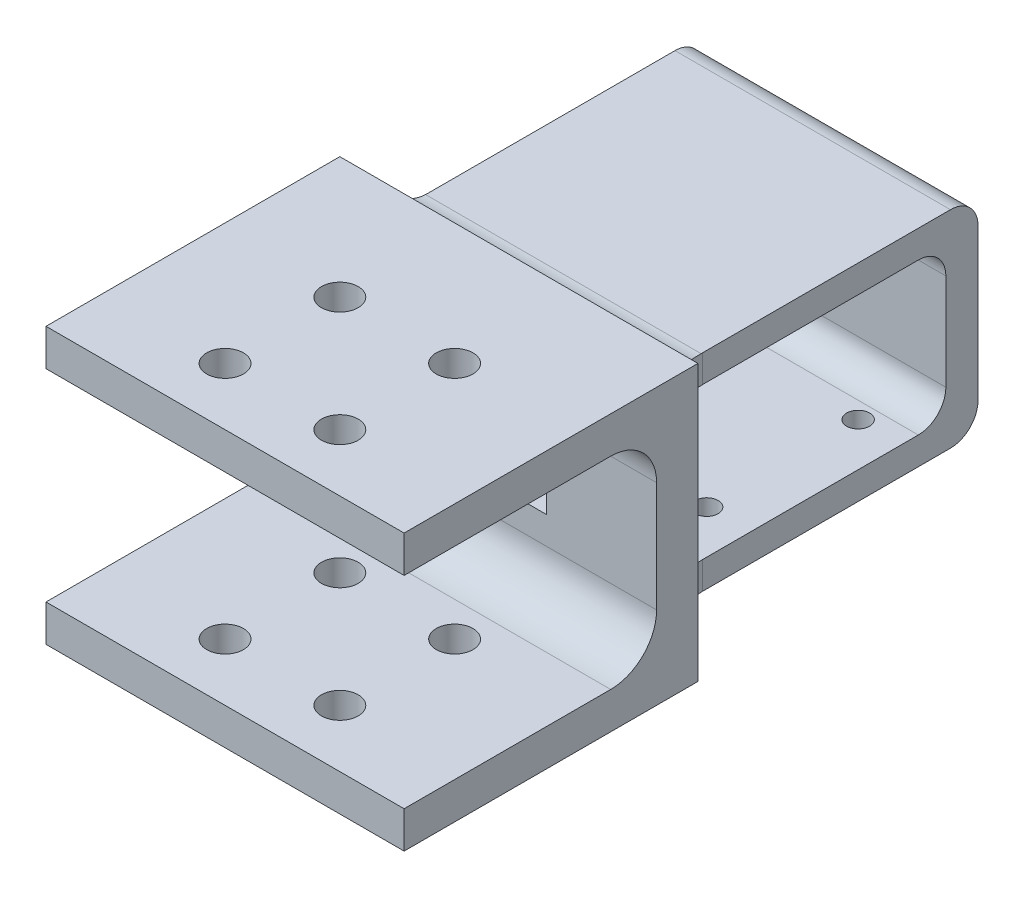
SolidWorks part; units mm, degrees
ref_plane "Front Plane" through (0, 0, 0) normal (0, 0, 1) x (1, 0, 0)
ref_plane "Top Plane" through (0, 0, 0) normal (0, 1, 0) x (1, 0, 0)
ref_plane "Right Plane" through (0, 0, 0) normal (1, 0, 0) x (0, 0, -1)
sketch "Sketch2" plane through (0, 0, 0) normal (0, 0, 1) x (1, 0, 0)
  line L1 (-20, 15) -> (20, 15)
  line L2 (-20, 15) -> (-20, -15)
  line L3 (-20, -15) -> (20, -15)
  line L4 (20, 15) -> (20, -15)
  line L5 (-20, 15) -> (20, -15) construction
  line L6 (-20, -15) -> (20, 15) construction
  point P0 (0, 0)
  dimension "D1" = 30
  dimension "D2" = 40
extrude "Boss-Extrude1" add sketch "Sketch2" along normal blind 40
sketch "Sketch3" plane through (-20, 0, 0) normal (-1, 0, 0) x (0, 0, 1)
  line L0 (0, 0) -> (40, 0) construction
  line L1 (40, 15) -> (40, -15) construction
  line L3 (0, 15) -> (0, -15) construction
  line L4 (40, 15) -> (0, 15) construction
  line L5 (9.5, 11) -> (40, 11)
  line L11 (9.5, -11) -> (40, -11)
  line L12 (4.5, 6) -> (4.5, -6)
  line L13 (40, 11) -> (40, -11)
  arc A2 (9.5, -11) -> (4.5, -6) centre (9.5, -6) cw
  arc A3 (4.5, 6) -> (9.5, 11) centre (9.5, 6) cw
  point P12 (4.5, -11)
  point P14 (0, 11)
  point P20 (4.5, 11)
  dimension "D2" = 5
  dimension "D1" = 4
  dimension "D3" = 4.5
extrude "Cut-Extrude4" cut sketch "Sketch3" against normal through all
fillet "Fillet1" radius 4 2 edges at (0, -15, 0) (0, 15, 0)
ref_plane "Plane1" through (-10, 0, 0) normal (-1, 0, 0) x (0, 0, 1)
sketch "Sketch4" plane through (-10, 0, 0) normal (-1, 0, 0) x (0, 0, 1)
  line L0 (0, 11) -> (-42.1, 11)
  line L1 (-42.1, -11) -> (1.4176, -11)
  line L7 (1.4176, -11) -> (1.4176, 11)
  line L17 (1.4176, 11) -> (0, 11)
  line L24 (0, 14.8516) -> (0, -23.2412) construction
  line L25 (-42.1, 11) -> (-42.1, -11)
  line L26 (-5, -6.1) -> (-37.1, -6.1)
  line L27 (-37.1, 6.1) -> (-37.1, -6.1)
  line L28 (-5, 6.1) -> (-37.1, 6.1)
  line L29 (-5, 6.1) -> (-5, -6.1)
  point P0 (-42.1, 0)
  point P26 (0, -11)
  point P27 (0, 11)
  dimension "D3" = 32.1
  dimension "D1" = 5
  dimension "D2" = 5
  dimension "D4" = 12.2
extrude "Boss-Extrude2" add sketch "Sketch4" along normal blind 8 and the other way blind 10
ref_plane "Plane2" through (-2.5, 0, 0) normal (1, 0, 0) x (0, 0, -1)
sketch "Sketch5" plane through (-2.5, 0, 0) normal (1, 0, 0) x (0, 0, -1)
  line L0 (37.1, -6.1) -> (5, -6.1) construction
  line L1 (5, 6.1) -> (9.2, 6.1)
  line L2 (5, 6.1) -> (5, -6.1)
  line L3 (5, -6.1) -> (9.2, -6.1)
  line L4 (9.2, 6.1) -> (9.2, -6.1)
  line L5 (21.05, 6.1) -> (21.05, -6.1) construction
  line L6 (5, 6.1) -> (37.1, 6.1) construction
  line L7 (32.9, 6.1) -> (32.9, -6.1)
  line L8 (37.1, -6.1) -> (32.9, -6.1)
  line L9 (37.1, 6.1) -> (37.1, -6.1)
  line L10 (37.1, 6.1) -> (32.9, 6.1)
  circle A2 centre (7.25, 0) radius 1.1
  circle A3 centre (34.85, 0) radius 1.1
  dimension "D1" = 4.2
  dimension "D2" = 27.6
extrude "Boss-Extrude3" add sketch "Sketch5" against normal blind 2.5
fillet "Fillet4" radius 0.5 2 edges at (-5, 0, -37.1) (-5, 0, -5)
sketch "Sketch6" plane through (0, 0, 0) normal (1, 0, 0) x (0, 0, -1)
  line L20 (37.8, -6.8) -> (37.8, 6.8)
  line L21 (37.8, 6.8) -> (4.3, 6.8)
  line L22 (4.3, 6.8) -> (4.3, -6.8)
  line L23 (4.3, -6.8) -> (37.8, -6.8)
  line L24 (37.8, -6.8) -> (37.8, 6.8)
  line L25 (37.8, 6.8) -> (4.3, 6.8)
  line L26 (4.3, 6.8) -> (4.3, -6.8)
  line L27 (4.3, -6.8) -> (37.8, -6.8)
  dimension "D1" = 0.7
extrude "Cut-Extrude5" cut sketch "Sketch6" against normal up to surface (2.5 mm away) up to face at (-2.5, 1.1, -7.25)
sketch "Sketch7" plane through (0, 0, -9.2) normal (0, 0, -1) x (-1, 0, 0)
  line L0 (5, 0) -> (15, 0) construction
  line L1 (5, -6.1) -> (5, 6.1) construction
  line L3 (12, 2.25) -> (15, 2.25)
  line L4 (12, 2.25) -> (12, -2.25)
  line L5 (12, -2.25) -> (15, -2.25)
  line L6 (15, 2.25) -> (15, -2.25)
  dimension "D1" = 10
  dimension "D2" = 4.5
  dimension "D3" = 3
extrude "Cut-Extrude6" cut sketch "Sketch7" against normal up to surface and the other way up to surface contours L6 L5 L4 L3 up to face at (0, 0, 4.5) other way up to face at (-9, 0, -42.1)
sketch "Sketch10" plane through (0, 0, 0) normal (1, 0, 0) x (0, 0, -1)
  line L1 (42.1, 11) -> (0, 11)
  line L2 (42.1, 11) -> (42.1, -11)
  line L3 (42.1, -11) -> (0, -11)
  line L4 (0, 11) -> (0, -11)
  line L5 (4.3, 6.8) -> (37.8, 6.8)
  line L6 (4.3, 6.8) -> (4.3, -6.8)
  line L7 (4.3, -6.8) -> (37.8, -6.8)
  line L8 (37.8, 6.8) -> (37.8, -6.8)
extrude "Boss-Extrude5" add sketch "Sketch10" along normal blind 5
fillet "Fillet7" radius 10 2 edges at (-6.5, 11, 0) (-6.5, -11, 0)
sketch "Sketch11" plane through (0, 0, -42.1) normal (0, 0, -1) x (-1, 0, 0)
  line L0 (18, 11) -> (-5, 11) construction
  line L1 (2, 11) -> (-8, 11)
  line L3 (2, -49) -> (-8, -49)
  line L4 (-8, 11) -> (-8, -49)
  line L5 (-5, 11) -> (-5, -11) construction
  line L6 (-5, 11) -> (-5, -11) construction
  line L7 (15, 2.25) -> (15, -2.25) construction
  line L8 (12, -2.25) -> (15, -2.25) construction
  line L9 (12, 2.25) -> (12, -2.25) construction
  line L10 (12, 2.25) -> (15, 2.25) construction
  line L11 (15, 2.25) -> (15, -2.25)
  line L12 (12, -2.25) -> (15, -2.25)
  line L13 (12, 2.25) -> (12, -2.25)
  line L14 (12, 2.25) -> (15, 2.25)
  line L15 (2, 11) -> (18, 11)
  line L16 (18, 11) -> (18, -49)
  line L17 (18, -49) -> (2, -49)
  dimension "D1" = 3
  dimension "D2" = 60
extrude "Boss-Extrude6" add sketch "Sketch11" along normal blind 20
sketch "Sketch14" plane through (0, 11, 0) normal (0, 1, 0) x (1, 0, 0)
  line L0 (1, 62.1) -> (1, 52.1) construction
  line L1 (-18, 62.1) -> (8, 62.1) construction
  line L2 (1, 52.1) -> (8, 52.1) construction
  line L3 (8, 62.1) -> (8, 42.1) construction
  line L4 (2, 55.1) -> (3, 55.1)
  line L6 (-1, 55.1) -> (-1, 49.1)
  line L7 (-1, 49.1) -> (3, 49.1)
  line L8 (3, 55.1) -> (3, 53.1)
  line L9 (-1, 55.1) -> (3, 49.1) construction
  line L10 (-1, 49.1) -> (3, 55.1) construction
  line L19 (3, 51.1) -> (3, 49.1)
  line L27 (0, 65.1) -> (2, 65.1)
  line L29 (0, 65.1) -> (0, 55.1)
  line L30 (2, 65.1) -> (2, 55.1)
  line L31 (3, 53.1) -> (13, 53.1)
  line L32 (13, 53.1) -> (13, 51.1)
  line L33 (13, 51.1) -> (3, 51.1)
  line L34 (-1, 55.1) -> (0, 55.1)
  point P7 (3, 50.1)
  dimension "D1" = 4
  dimension "D2" = 6
  dimension "D3" = 2
  dimension "D4" = 2
  dimension "D5" = 10
  dimension "D6" = 10
  dimension "D7" = 5
extrude "Cut-Extrude7" cut sketch "Sketch14" against normal blind 50
sketch "Sketch17" plane through (0, -39, 0) normal (0, 1, 0) x (1, 0, 0)
  line L1 (-1, 55.1) -> (3, 55.1)
  line L2 (-1, 55.1) -> (-1, 49.1)
  line L3 (-1, 49.1) -> (3, 49.1)
  line L4 (3, 55.1) -> (3, 49.1)
extrude "Cut-Extrude8" cut sketch "Sketch17" against normal blind 1
sketch "Sketch18" plane through (0, 11, 0) normal (0, 1, 0) x (1, 0, 0)
  line L5 (-17, 61.1) -> (7, 61.1)
  line L6 (7, 61.1) -> (7, 43.1)
  line L7 (-17, 43.1) -> (7, 43.1)
  line L8 (-17, 61.1) -> (-17, 43.1)
  line L9 (-18, 5.798) -> (-18, 62.1) construction
  line L10 (-18, 62.1) -> (0, 62.1) construction
  line L11 (8, 51.1) -> (8, 42.1) construction
  line L12 (5, 42.1) -> (8, 42.1) construction
  dimension "D1" = 1
  dimension "D2" = 1
  dimension "D3" = 1
  dimension "D4" = 1
extrude "Cut-Extrude9" cut sketch "Sketch18" against normal blind 1
sketch "Sketch20" plane through (0, 15, 0) normal (0, 1, 0) x (1, 0, 0)
  line L0 (-17.0807, -4) -> (-17.0807, -40) construction
  line L1 (-23.2772, -29) -> (21.5631, -29)
  line L2 (-23.2772, -29) -> (-23.2772, -45.2236)
  line L3 (-23.2772, -45.2236) -> (21.5631, -45.2236)
  line L4 (21.5631, -29) -> (21.5631, -45.2236)
  line L5 (20, -4) -> (-20, -4) construction
  line L6 (20, -40) -> (-20, -40) construction
  dimension "D1" = 36
  dimension "D2" = 25
extrude "Cut-Extrude10" cut sketch "Sketch20" against normal through all
sketch "Sketch23" plane through (-20, 0, 0) normal (-1, 0, 0) x (0, 0, 1)
  line L0 (4.5, 0) -> (34.0631, 0) construction
  line L1 (29, 15) -> (32, 15)
  line L2 (29, 15) -> (29, 11)
  line L3 (29, 11) -> (32, 11)
  line L4 (32, 15) -> (32, 11)
  line L5 (4.5, 6) -> (4.5, -6) construction
  line L6 (29, 11) -> (9.5, 11) construction
  line L7 (32, -15) -> (32, -11)
  line L8 (29, -11) -> (32, -11)
  line L9 (29, -15) -> (29, -11)
  line L10 (29, -15) -> (32, -15)
  dimension "D1" = 3
extrude "Boss-Extrude7" add sketch "Sketch23" against normal up to surface (40 mm away) up to face at (20, 0, 12.356)
sketch "Sketch24" plane through (20, 0, 0) normal (1, 0, 0) x (0, 0, -1)
  line L1 (0, 22.9048) -> (-36.376, 22.9048)
  line L2 (0, 22.9048) -> (0, -20.1823)
  line L3 (0, -20.1823) -> (-36.376, -20.1823)
  line L4 (-36.376, 22.9048) -> (-36.376, -20.1823)
extrude "Cut-Extrude13" cut sketch "Sketch24" against normal up to surface (15 mm away) up to face at (5, 0, -11.6762)
sketch "Sketch25" plane through (-20, 0, 0) normal (-1, 0, 0) x (0, 0, 1)
  line L1 (0, 22.5734) -> (34.945, 22.5734)
  line L2 (0, 22.5734) -> (0, -21.6266)
  line L3 (0, -21.6266) -> (34.945, -21.6266)
  line L4 (34.945, 22.5734) -> (34.945, -21.6266)
extrude "Cut-Extrude14" cut sketch "Sketch25" against normal up to surface (2 mm away) up to face at (-18, 0, -21.05)
ref_plane "Plane3" through (-6.5, 0, 0) normal (-1, 0, 0) x (0, 0, 1)
sketch "Sketch26" plane through (-6.5, 0, 0) normal (-1, 0, 0) x (0, 0, 1)
  line L0 (1.2006, 13.8571) -> (1.2006, -13.8571)
  line L50 (4, -15) -> (32, -15)
  line L51 (32, -15) -> (32, -11)
  line L52 (32, -11) -> (9.5, -11)
  line L53 (4.5, -6) -> (4.5, 6)
  line L54 (9.5, 11) -> (32, 11)
  line L55 (32, 11) -> (32, 15)
  line L56 (32, 15) -> (4, 15)
  line L57 (4, -15) -> (32, -15)
  line L58 (32, -15) -> (32, -11)
  line L59 (32, -11) -> (9.5, -11)
  line L60 (4.5, -6) -> (4.5, 6)
  line L61 (9.5, 11) -> (32, 11)
  line L62 (32, 11) -> (32, 15)
  line L63 (32, 15) -> (4, 15)
  arc A0 (1.2006, -13.8571) -> (-5.798, -11) centre (-5.798, -21) ccw construction
  arc A29 (1.2006, -13.8571) -> (4, -15) centre (4, -11) ccw
  arc A30 (4.5, -6) -> (9.5, -11) centre (9.5, -6) ccw
  arc A31 (9.5, 11) -> (4.5, 6) centre (9.5, 6) ccw
  arc A32 (4, 15) -> (1.2006, 13.8571) centre (4, 11) ccw
  arc A33 (1.2006, -13.8571) -> (4, -15) centre (4, -11) ccw
  arc A34 (4.5, -6) -> (9.5, -11) centre (9.5, -6) ccw
  arc A35 (9.5, 11) -> (4.5, 6) centre (9.5, 6) ccw
  arc A36 (4, 15) -> (1.2006, 13.8571) centre (4, 11) ccw
  dimension "D1" = 0
extrude "Boss-Extrude8" add sketch "Sketch26" along normal blind 20 and the other way blind 20
sketch "Sketch27" plane through (0, 0, -62.1) normal (0, 0, -1) x (-1, 0, 0)
  line L0 (12, -2.25) -> (15, -2.25) construction
  line L1 (15, -2.25) -> (15, 2.25) construction
  line L2 (15, 2.25) -> (12, 2.25) construction
  line L3 (12, -2.25) -> (12, 2.25) construction
  line L4 (12, -2.25) -> (15, -2.25)
  line L5 (15, -2.25) -> (15, 2.25)
  line L6 (15, 2.25) -> (12, 2.25)
  line L7 (12, -2.25) -> (12, 2.25)
extrude "Cut-Extrude15" cut sketch "Sketch27" against normal through all
sketch "Sketch30" plane through (0, 10, 0) normal (0, 1, 0) x (1, 0, 0)
  line L0 (-5, 43.1) -> (-5, 61.1) construction
  line L1 (-17, 43.1) -> (7, 43.1) construction
  line L2 (0, 61.1) -> (-17, 61.1) construction
  line L3 (-17, 52.1) -> (8, 52.1) construction
  line L4 (-17, 61.1) -> (-17, 43.1) construction
  line L5 (8, 51.1) -> (8, 53.1) construction
  line L6 (7, 61.1) -> (2, 61.1) construction
  line L7 (7, 53.1) -> (7, 61.1) construction
  circle A0 centre (5, 58.1) radius 1.2
  circle A1 centre (5, 46.1) radius 1.2
  circle A2 centre (-15, 58.1) radius 1.2
  circle A3 centre (-15, 46.1) radius 1.2
  dimension "D1" = 3
  dimension "D2" = 2
extrude "Cut-Extrude16" cut sketch "Sketch30" against normal blind 5
sketch "Sketch31" plane through (8, 0, 0) normal (1, 0, 0) x (0, 0, -1)
  line L0 (62.1, 11) -> (62.1, -49) construction
  line L1 (42.1, -49) -> (62.1, -49)
  line L2 (42.1, -49) -> (42.1, -44)
  line L3 (42.1, -44) -> (62.1, -44)
  line L4 (62.1, -49) -> (62.1, -44)
  dimension "D1" = 5
extrude "Cut-Extrude17" cut sketch "Sketch31" against normal through all
sketch "Sketch32" plane through (0, -11, 0) normal (0, 1, 0) x (1, 0, 0)
  line L0 (-6.5, -9.5) -> (-6.5, -32) construction
  line L5 (13.5, -9.5) -> (-26.5, -9.5) construction
  line L6 (13.5, -32) -> (-26.5, -32) construction
  line L7 (-26.5, -20.75) -> (-6.5, -20.75) construction
  line L8 (-26.5, -32) -> (-26.5, -9.5) construction
  line L9 (-16.5, -20.75) -> (-16.5, -32) construction
  line L10 (-16.5, -20.75) -> (-16.5, -9.5) construction
  line L11 (3.5, -20.75) -> (3.5, -32) construction
  line L12 (3.5, -20.75) -> (3.5, -9.5) construction
  line L13 (13.5, -20.75) -> (-6.5, -20.75) construction
  circle A0 centre (-16.5, -26.375) radius 2
  circle A1 centre (-16.5, -15.125) radius 2
  circle A2 centre (3.5, -26.375) radius 2
  circle A3 centre (3.5, -15.125) radius 2
extrude "Cut-Extrude18" cut sketch "Sketch32" against normal blind 10 and the other way through all
sketch "Sketch35" plane through (0, 15, 0) normal (0, 1, 0) x (1, 0, 0)
  line L0 (-6.5, -4) -> (-6.5, -32) construction
  line L1 (13.5, -4) -> (-26.5, -4) construction
  line L2 (13.5, -32) -> (-26.5, -32) construction
  line L3 (-26, -32) -> (13, -32) construction
  line L4 (13, 0) -> (13, -33.7199)
  line L5 (-29.2566, 0) -> (-26, 0)
  line L6 (-29.2566, 0) -> (-29.2566, -33.7199)
  line L7 (-29.2566, -33.7199) -> (-26, -33.7199)
  line L8 (-26, 0) -> (-26, -33.7199)
  line L9 (16.2566, -33.7199) -> (13, -33.7199)
  line L10 (16.2566, 0) -> (16.2566, -33.7199)
  line L11 (16.2566, 0) -> (13, 0)
  dimension "D1" = 39
extrude "Cut-Extrude19" cut sketch "Sketch35" against normal through all
sketch "Sketch36" plane through (0, 15, 0) normal (0, 1, 0) x (1, 0, 0)
  circle A0 centre (-16.5, -15.125) radius 2
  circle A1 centre (3.5, -15.125) radius 2
  circle A2 centre (3.5, -26.375) radius 2
  circle A3 centre (-16.5, -26.375) radius 2
extrude "Boss-Extrude9" add sketch "Sketch36" against normal up to surface (30 mm away) up to face at (-16.5, -15, 17.125)
sketch "Sketch37" plane through (0, 15, 0) normal (0, 1, 0) x (1, 0, 0)
  line L0 (-6.5, -32) -> (-6.5, -4) construction
  line L1 (13, -32) -> (-26, -32) construction
  line L2 (13, -4) -> (-26, -4) construction
  line L3 (-19, -19.5) -> (-6.5, -19.5) construction
  line L4 (-19, -32) -> (6, -32) construction
  line L5 (-19, -32) -> (-19, -7) construction
  line L6 (-19, -7) -> (6, -7) construction
  line L7 (6, -32) -> (6, -7) construction
  line L8 (-12.75, -19.5) -> (-12.75, -32) construction
  circle A0 centre (-12.75, -25.75) radius 2
  circle A1 centre (-0.25, -25.75) radius 2
  circle A2 centre (-0.25, -13.25) radius 2
  circle A3 centre (-12.75, -13.25) radius 2
  dimension "D1" = 25
  dimension "D2" = 25
extrude "Cut-Extrude20" cut sketch "Sketch37" against normal through all
sketch "Sketch38" plane through (13, 0, 0) normal (1, 0, 0) x (0, 0, -1)
  line L1 (-32, 11) -> (-11.25, 11)
  line L2 (-32, 11) -> (-32, -11)
  line L3 (-32, -11) -> (-11.25, -11)
  line L4 (-11.25, 11) -> (-11.25, -11)
extrude "Cut-Extrude21" cut sketch "Sketch38" against normal through all
sketch "Sketch39" plane through (13, 0, 0) normal (1, 0, 0) x (0, 0, -1)
  line L1 (-2.2508, 19.3242) -> (69.9797, 19.3242)
  line L2 (-2.2508, 19.3242) -> (-2.2508, -51.109)
  line L3 (-2.2508, -51.109) -> (69.9797, -51.109)
  line L4 (69.9797, 19.3242) -> (69.9797, -51.109)
extrude "Cut-Extrude22" cut sketch "Sketch39" against normal through all
sketch "Sketch40" plane through (13, 0, 0) normal (1, 0, 0) x (0, 0, -1)
  line L0 (-4, 15) -> (0, 15)
  line L1 (0, 15) -> (0, -15)
  line L2 (0, -15) -> (-4, -15)
  line L3 (-4, 15) -> (-4, -15)
  dimension "D1" = 4
extrude "Boss-Extrude10" add sketch "Sketch40" against normal up to surface (39 mm away) up to face at (-26, 0, 13.8654)
ref_plane "Plane4" through (-6.5, 0, 0) normal (-1, 0, 0) x (0, 0, 1)
sketch "Sketch41" plane through (-6.5, 0, 0) normal (-1, 0, 0) x (0, 0, 1)
  line L0 (-21.4, 15) -> (-3, 15)
  line L1 (-18.4, 12) -> (-6, 12)
  line L2 (-18.4, 12) -> (-18.4, -20.6)
  line L3 (-18.4, -20.6) -> (-6, -20.6)
  line L4 (-6, 12) -> (-6, -20.6)
  line L5 (-3, -15) -> (-3, -23.6)
  line L6 (-21.4, -23.6) -> (-3, -23.6)
  line L7 (-21.4, 15) -> (-21.4, -23.6)
  line L8 (32, 15) -> (0, 15) construction
  line L9 (0, 15) -> (0, -15) construction
  line L10 (-3, 15) -> (0, 15)
  line L11 (0, -15) -> (-3, -15)
  line L12 (0, -15) -> (1.5471, -15)
  line L13 (32, -15) -> (0, -15) construction
  line L14 (1.5471, -15) -> (1.5471, 15)
  line L15 (1.5471, 15) -> (0, 15)
  line L17 (-3, 15) -> (-3, -23.6) construction
  dimension "D1" = 32.6
  dimension "D2" = 12.4
  dimension "D4" = 3
  dimension "D3" = 3
extrude "Boss-Extrude11" add sketch "Sketch41" along normal blind 10 and the other way blind 5
sketch "Sketch42" plane through (-6.5, 0, 0) normal (-1, 0, 0) x (0, 0, 1)
  line L0 (-12.2, 12) -> (-12.2, 9.5) construction
  line L1 (-6, 12) -> (-18.4, 12) construction
  line L2 (-6, -20.6) -> (-6, 12) construction
  line L3 (-18.4, 12) -> (-6, 12)
  line L4 (-18.4, 12) -> (-18.4, 8)
  line L5 (-18.4, 8) -> (-6, 8)
  line L6 (-6, 12) -> (-6, 8)
  line L7 (-18.4, -4.3) -> (-6, -4.3) construction
  line L8 (-18.4, 12) -> (-18.4, -20.6) construction
  line L9 (-12.2, -20.6) -> (-12.2, -18.1) construction
  line L10 (-6, -20.6) -> (-6, -16.6)
  line L11 (-18.4, -16.6) -> (-6, -16.6)
  line L12 (-18.4, -20.6) -> (-18.4, -16.6)
  line L13 (-18.4, -20.6) -> (-6, -20.6)
  circle A0 centre (-12.2, 9.5) radius 1
  circle A1 centre (-12.2, -18.1) radius 1
  dimension "D1" = 2.5
  dimension "D2" = 4
extrude "Boss-Extrude12" add sketch "Sketch42" against normal blind 1 and the other way blind 1
sketch "Sketch43" plane through (-6.5, 0, 0) normal (-1, 0, 0) x (0, 0, 1)
  line L1 (-21.4, -23.6) -> (-36.4, -23.6)
  line L2 (-21.4, -23.6) -> (-21.4, 1.4)
  line L3 (-21.4, 1.4) -> (-36.4, 1.4)
  line L4 (-36.4, -23.6) -> (-36.4, 1.4)
  dimension "D1" = 25
  dimension "D2" = 15
extrude "Boss-Extrude13" add sketch "Sketch43" against normal up to surface (5 mm away) and the other way up to surface (10 mm away) up to face at (-1.5, -7.8667, -8.1333) other way up to face at (-16.5, -7.8667, -8.1333)
sketch "Sketch44" plane through (0, 1.4, 0) normal (0, 1, 0) x (1, 0, 0)
  line L3 (-9, 36.4) -> (-9, 21.4) construction
  line L4 (-1.5, 36.4) -> (-16.5, 36.4) construction
  line L6 (-1.5, 21.4) -> (-16.5, 21.4) construction
  line L8 (-9, 30.9) -> (-1.5, 30.9) construction
  line L9 (-11, 33.9) -> (-10.0516, 33.9)
  line L10 (-11, 33.9) -> (-11, 31.9)
  line L11 (-11, 27.9) -> (-7, 27.9)
  line L12 (-7, 33.9) -> (-7, 31.9)
  line L13 (-11, 33.9) -> (-7, 27.9) construction
  line L14 (-11, 27.9) -> (-7, 33.9) construction
  line L15 (-10.0516, 38.217) -> (-7.989, 38.217)
  line L16 (-10.0516, 38.217) -> (-10.0516, 33.9)
  line L18 (-7.989, 38.217) -> (-7.989, 33.9)
  line L19 (0.8667, 31.9) -> (-7, 31.9)
  line L20 (0.8667, 31.9) -> (0.8667, 29.9)
  line L21 (0.8667, 29.9) -> (-7, 29.9)
  line L23 (-1.5, 36.4) -> (-1.5, 21.4) construction
  line L24 (-7, 29.9) -> (-7, 27.9)
  line L25 (-7.989, 33.9) -> (-7, 33.9)
  line L26 (-18.8667, 29.9) -> (-11, 29.9)
  line L27 (-18.8667, 31.9) -> (-18.8667, 29.9)
  line L28 (-18.8667, 31.9) -> (-11, 31.9)
  line L29 (-11, 29.9) -> (-11, 27.9)
  point P6 (-9, 30.9)
  dimension "D1" = 4
  dimension "D2" = 6
  dimension "D3" = 2.5
  dimension "D4" = 2
extrude "Cut-Extrude23" cut sketch "Sketch44" against normal through all
sketch "Sketch45" plane through (0, 1.4, 0) normal (0, 1, 0) x (1, 0, 0)
  line L1 (-11, 33.9) -> (-10.0516, 33.9)
  line L2 (-11, 33.9) -> (-11, 31.9)
  line L3 (-11, 27.9) -> (-7, 27.9)
  line L4 (-7, 33.9) -> (-7, 31.9)
  line L16 (-11, 29.9) -> (-11, 27.9)
  line L17 (-7.989, 33.9) -> (-7, 33.9)
  line L18 (-7, 29.9) -> (-7, 27.9)
  line L19 (-16.5, 31.7) -> (-16.5, 30.1)
  line L20 (-1.5, 31.7) -> (-1.5, 30.1)
  line L21 (-9.8516, 36.4) -> (-8.189, 36.4)
  line L22 (-11, 31.7) -> (-16.5, 31.7)
  line L23 (-16.5, 30.1) -> (-11, 30.1)
  line L24 (-9.8516, 36.4) -> (-9.8516, 33.9)
  line L25 (-8.189, 33.9) -> (-8.189, 36.4)
  line L26 (-1.5, 31.7) -> (-7, 31.7)
  line L27 (-7, 30.1) -> (-1.5, 30.1)
  line L28 (-11, 31.7) -> (-11, 31.9)
  line L29 (-11, 30.1) -> (-11, 29.9)
  line L30 (-9.8516, 33.9) -> (-10.0516, 33.9)
  line L31 (-8.189, 33.9) -> (-7.989, 33.9)
  line L32 (-7, 31.9) -> (-7, 31.7)
  line L33 (-7, 30.1) -> (-7, 29.9)
extrude "Boss-Extrude15" add sketch "Sketch45" along normal blind 1.5 and the other way blind 0.5
sketch "Sketch46" plane through (0, 2.9, 0) normal (0, 1, 0) x (1, 0, 0)
  line L0 (-1.5, 29.9) -> (-1.5, 21.4) construction
  line L1 (-16.5, 36.4) -> (-1.5, 36.4)
  line L2 (-16.5, 36.4) -> (-16.5, 25.65)
  line L3 (-16.5, 25.65) -> (-1.5, 25.65)
  line L4 (-1.5, 36.4) -> (-1.5, 25.65)
extrude "Boss-Extrude16" add sketch "Sketch46" against normal blind 1.45
ref_plane "Plane5" through (0, -11.1, 0) normal (0, 1, 0) x (1, 0, 0)
mirror "Mirror1" about plane through (0, -11.1, 0) normal (0, 1, 0) of "Boss-Extrude15"
sketch "Sketch47" plane through (0, -25.1, 0) normal (0, -1, 0) x (1, 0, 0)
  line L0 (-16.5, -29.9) -> (-16.5, -3) construction
  line L1 (-1.5, -36.4) -> (-16.5, -36.4)
  line L2 (-1.5, -36.4) -> (-1.5, -25.65)
  line L3 (-1.5, -25.65) -> (-16.5, -25.65)
  line L4 (-16.5, -36.4) -> (-16.5, -25.65)
  dimension "D1" = 10.75
extrude "Boss-Extrude17" add sketch "Sketch47" against normal blind 1.45
sketch "Sketch48" plane through (13, 0, 0) normal (1, 0, 0) x (0, 0, -1)
  line L1 (0, 15) -> (36.4, 15)
  line L2 (0, 15) -> (0, -25.1)
  line L3 (0, -25.1) -> (36.4, -25.1)
  line L4 (36.4, 15) -> (36.4, -25.1)
extrude "Cut-Extrude24" cut sketch "Sketch48" against normal through all
sketch "Sketch49" plane through (0, 0, 4.5) normal (0, 0, 1) x (1, 0, 0)
  line L1 (-26, 6) -> (13, 6)
  line L2 (-26, 6) -> (-26, -6)
  line L3 (-26, -6) -> (13, -6)
  line L4 (13, 6) -> (13, -6)
extrude "Cut-Extrude25" cut sketch "Sketch49" against normal through all
sketch "Sketch50" plane through (0, -6, 0) normal (0, 1, 0) x (1, 0, 0)
  line L4 (-26, -4.5) -> (13, -4.5)
  line L5 (13, -4.5) -> (13, 0)
  line L6 (13, 0) -> (-26, 0)
  line L7 (-26, 0) -> (-26, -4.5)
  line L8 (-26, -4.5) -> (13, -4.5)
  line L9 (13, -4.5) -> (13, 0)
  line L10 (13, 0) -> (-26, 0)
  line L11 (-26, 0) -> (-26, -4.5)
  dimension "D1" = 0
extrude "Boss-Extrude18" add sketch "Sketch50" along normal up to surface (12 mm away) up to face at (-6.5, 6, 2.25)
sketch "Sketch51" plane through (0, 0, 0) normal (0, 0, -1) x (-1, 0, 0)
  line L0 (6.5, 15) -> (6.5, -15) construction
  line L1 (26, 15) -> (-13, 15) construction
  line L2 (26, -15) -> (-13, -15) construction
  line L3 (-13, 0) -> (26, 0) construction
  line L4 (26, 15) -> (26, -15) construction
  line L5 (-8.5, 8.25) -> (21.5, 8.25)
  line L6 (-8.5, 11.25) -> (21.5, 11.25)
  line L7 (-8.5, 11.25) -> (-8.5, 8.25)
  line L8 (-8.5, -11.25) -> (21.5, -11.25)
  line L9 (21.5, 11.25) -> (21.5, 8.25)
  line L10 (-8.5, 11.25) -> (21.5, -11.25) construction
  line L11 (-8.5, -11.25) -> (21.5, 11.25) construction
  line L12 (-8.5, -8.25) -> (21.5, -8.25)
  line L13 (-8.5, -8.25) -> (-8.5, -11.25)
  line L14 (21.5, -8.25) -> (21.5, -11.25)
  point P6 (6.5, 0)
  point P11 (6.5, 0)
  dimension "D1" = 30
  dimension "D2" = 22.5
  dimension "D3" = 3
extrude "Boss-Extrude19" add sketch "Sketch51" along normal blind 35
sketch "Sketch52" plane through (8.5, 0, 0) normal (1, 0, 0) x (0, 0, -1)
  line L0 (35, -11.25) -> (0, -11.25) construction
  line L1 (35, 11.25) -> (31.5, 11.25)
  line L2 (35, 11.25) -> (35, -11.25)
  line L3 (35, -11.25) -> (31.5, -11.25)
  line L4 (31.5, 11.25) -> (31.5, -11.25)
  dimension "D1" = 3.5
extrude "Boss-Extrude20" add sketch "Sketch52" against normal up to surface (30 mm away) up to face at (-21.5, 9.75, -17.5)
fillet "Fillet8" radius 3 2 edges at (-6.5, -11.25, -35) (-6.5, 11.25, -35)
fillet "Fillet9" radius 3 2 edges at (-6.5, 8.25, -31.5) (-6.5, -8.25, -31.5)
sketch "Sketch53" plane through (0, 0, 4.5) normal (0, 0, 1) x (1, 0, 0)
  line L0 (-6.5, 6) -> (-6.5, -6) construction
  line L1 (13, 6) -> (-26, 6) construction
  line L2 (-26, -6) -> (13, -6) construction
  line L4 (-14, 3) -> (1, 3)
  line L5 (-14, 3) -> (-14, -3)
  line L6 (-14, -3) -> (1, -3)
  line L7 (1, 3) -> (1, -3)
  line L8 (-14, 3) -> (1, -3) construction
  line L9 (-14, -3) -> (1, 3) construction
  point P6 (-6.5, 0)
  dimension "D1" = 15
  dimension "D2" = 6
extrude "Cut-Extrude26" cut sketch "Sketch53" against normal up to surface (4.5 mm away) up to face at (-6.5, 0, 0)
fillet "Fillet10" radius 5 6 edges at (8.5, -9.75, 0) (8.5, 9.75, 0) (-21.5, 9.75, 0) (-21.5, -9.75, 0) (-6.5, -11.25, 0) (-6.5, 11.25, 0)
sketch "Sketch54" plane through (0, -11.25, 0) normal (0, -1, 0) x (1, 0, 0)
  line L0 (-6.5, -7.1706) -> (-6.5, -29.6706) construction
  line L1 (-19.775, -18.4206) -> (6.775, -18.4206) construction
  line L2 (-19.775, -9.1706) -> (-17.775, -9.1706) construction
  line L3 (-17.775, -9.1706) -> (-17.775, -7.1706) construction
  line L4 (4.775, -7.1706) -> (4.775, -9.1706) construction
  line L5 (4.775, -9.1706) -> (6.775, -9.1706) construction
  line L6 (4.775, -29.6706) -> (4.775, -27.6706) construction
  line L7 (4.775, -27.6706) -> (6.775, -27.6706) construction
  line L8 (6.775, -27.6706) -> (6.775, -9.1706) construction
  line L9 (4.775, -7.1706) -> (-17.775, -7.1706) construction
  line L10 (-19.775, -9.1706) -> (-19.775, -27.6706) construction
  line L11 (-17.775, -29.6706) -> (4.775, -29.6706) construction
  line L12 (-19.775, -27.6706) -> (-17.775, -27.6706) construction
  line L13 (-17.775, -27.6706) -> (-17.775, -29.6706) construction
  line L14 (-6.5, -4.8412) -> (-6.5, -32) construction
  line L15 (8.5018, -4.8412) -> (-21.5018, -4.8412) construction
  line L16 (-21.5, -32) -> (8.5, -32) construction
  circle A0 centre (-16.775, -10.1706) radius 1.25
  circle A1 centre (3.775, -10.1706) radius 1.25
  circle A2 centre (3.775, -26.6706) radius 1.25
  circle A3 centre (-16.775, -26.6706) radius 1.25
  arc A4 (4.775, -29.6706) -> (6.775, -27.6706) centre (4.775, -27.6706) ccw construction
  arc A5 (6.775, -9.1706) -> (4.775, -7.1706) centre (4.775, -9.1706) ccw construction
  arc A6 (-17.775, -7.1706) -> (-19.775, -9.1706) centre (-17.775, -9.1706) ccw construction
  arc A7 (-19.775, -27.6706) -> (-17.775, -29.6706) centre (-17.775, -27.6706) ccw construction
  point P15 (-6.5, -18.4206)
  point P31 (-6.5, -18.4206)
  dimension "D3" = 2
  dimension "D4" = 2
  dimension "D5" = 2
  dimension "D6" = 2
  dimension "D7" = 2.5
  dimension "D1" = 26.55
  dimension "D2" = 22.5
  dimension "D8" = 3
  dimension "D9" = 3
extrude "Cut-Extrude27" cut sketch "Sketch54" against normal up to surface (3 mm away) up to face at (-6.5, -8.25, -10.8694)
